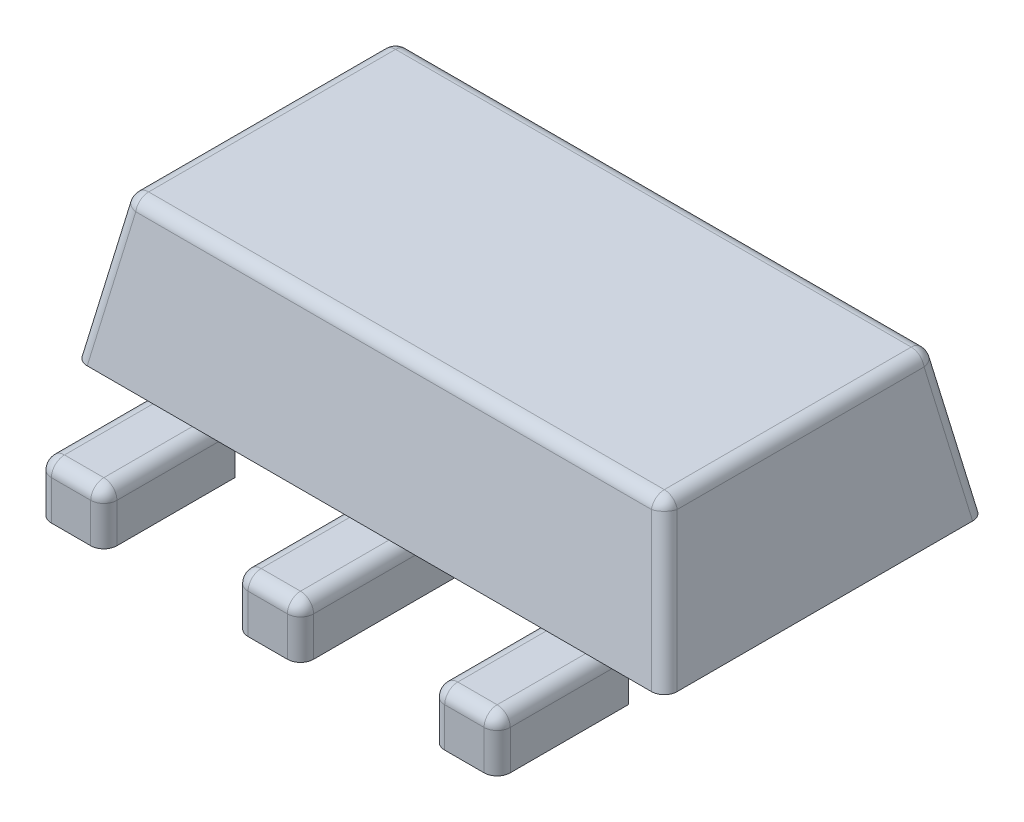
SolidWorks part; units mm, degrees
ref_plane "Спереди" through (0, 0, 0) normal (0, 0, 1) x (1, 0, 0)
ref_plane "Сверху" through (0, 0, 0) normal (0, 1, 0) x (1, 0, 0)
ref_plane "Справа" through (0, 0, 0) normal (1, 0, 0) x (0, 0, -1)
sketch "Эскиз1" plane through (0, 0, 0) normal (0, 1, 0) x (1, 0, 0)
  line L0 (-0.2499, -1) -> (-0.2499, -0.6205)
  line L1 (-1.75, -1) -> (-1.25, -1)
  line L2 (-1.75, -1) -> (-1.75, -2)
  line L3 (-1.75, -2) -> (-1.25, -2)
  line L4 (-1.25, -1) -> (-1.25, -2)
  line L5 (-1.75, -1) -> (-1.25, -2) construction
  line L6 (-1.75, -2) -> (-1.25, -1) construction
  line L7 (1.25, -1) -> (1.75, -1)
  line L8 (1.25, -1) -> (1.25, -2)
  line L9 (1.25, -2) -> (1.75, -2)
  line L10 (1.75, -1) -> (1.75, -2)
  line L11 (1.25, -1) -> (1.75, -2) construction
  line L12 (1.25, -2) -> (1.75, -1) construction
  line L13 (0.2499, -2) -> (-0.2499, -2)
  line L14 (0.2499, -2) -> (0.2499, -1)
  line L15 (-0.3378, -0.4084) -> (-0.7263, -0.02)
  line L16 (-0.2499, -2) -> (-0.2499, -1)
  line L17 (0.2499, -2) -> (-0.2499, -1) construction
  line L18 (0.2499, -1) -> (0.2499, -0.7278)
  line L19 (0.3179, -0.5376) -> (0.7462, -0.015)
  line L20 (0.2499, -1) -> (-0.2499, -2) construction
  line L21 (-0.5141, 2) -> (0.5141, 2)
  line L22 (-0.8141, 1.7) -> (-0.8141, 0.1922)
  line L25 (0.8141, 1.7) -> (0.8141, 0.1751)
  arc A0 (-0.2499, -0.6205) -> (-0.3378, -0.4084) centre (-0.5499, -0.6205) ccw
  arc A1 (0.2499, -0.7278) -> (0.3179, -0.5376) centre (0.5499, -0.7278) cw
  arc A2 (0.5141, 2) -> (0.8141, 1.7) centre (0.5141, 1.7) cw
  arc A3 (-0.8141, 1.7) -> (-0.5141, 2) centre (-0.5141, 1.7) cw
  arc A4 (0.7462, -0.015) -> (0.8141, 0.1751) centre (0.5141, 0.1751) ccw
  arc A5 (-0.7263, -0.02) -> (-0.8141, 0.1922) centre (-0.5141, 0.1922) cw
  point P0 (-1.5, -1.5)
  point P5 (1.5, -1.5)
  point P15 (0, 0.5)
  point P25 (0, 0)
  point P26 (0, -1.5)
  point P35 (0, 0)
  point P36 (0, 0)
  dimension "D1" = 0.3
  dimension "D2" = 0.3
  dimension "D3" = 0.3
  dimension "D4" = 0.3
extrude "Бобышка-Вытянуть1" add sketch "Эскиз1" along normal blind 0.4
fillet "Скругление1" radius 0.1 16 edges at (-0.532, 0.4, 0.2142) (-0.7913, 0.4, -0.0774) (-0.8141, 0.4, -0.9461) (-0.7263, 0.4, -1.9121) (0, 0.4, -2) (0.7263, 0.4, -1.9121) (0.8141, 0.4, -0.9376) (0.7966, 0.4, -0.0742) (0.532, 0.4, 0.2763) (0.2674, 0.4, 0.6268) (0.2499, 0.4, 1.3639) (0, 0.4, 2) (-0.2499, 0.4, 1.3103) (-0.2728, 0.4, 0.5057) (0.2499, 0.2, 2) (-0.2499, 0.2, 2)
fillet "Скругление2" radius 0.1 6 edges at (-1.5, 0.4, 2) (-1.75, 0.4, 1.5) (-1.5, 0.4, 1) (-1.25, 0.4, 1.5) (-1.25, 0.2, 2) (-1.75, 0.2, 2)
fillet "Скругление3" radius 0.1 6 edges at (1.5, 0.4, 2) (1.25, 0.4, 1.5) (1.5, 0.4, 1) (1.75, 0.4, 1.5) (1.75, 0.2, 2) (1.25, 0.2, 2)
sketch "Эскиз2" plane through (0, 0.4, 0) normal (0, 1, 0) x (1, 0, 0)
  line L1 (-2.25, 1.225) -> (2.25, 1.225)
  line L2 (-2.25, 1.225) -> (-2.25, -1.225)
  line L3 (-2.25, -1.225) -> (2.25, -1.225)
  line L4 (2.25, 1.225) -> (2.25, -1.225)
  line L5 (-2.25, 1.225) -> (2.25, -1.225) construction
  line L6 (-2.25, -1.225) -> (2.25, 1.225) construction
  point P0 (0, 0)
extrude "Бобышка-Вытянуть2" add sketch "Эскиз2" along normal blind 1.1 separate body
chamfer "Фаска1" distance 1.1 distance2 0.2 4 edges at (0, 1.5, 1.225) (-2.25, 1.5, 0) (0, 1.5, -1.225) (2.25, 1.5, 0) first distance on face at (0, 0.95, 1.225) first distance on face at (-2.25, 0.95, 0) first distance on face at (0, 0.95, -1.225) first distance on face at (2.25, 0.95, 0)
fillet "Скругление4" radius 0.1 8 edges at (0, 1.5, -1.025) (2.05, 1.5, 0) (0, 1.5, 1.025) (-2.05, 1.5, 0) (-2.15, 0.95, -1.125) (-2.15, 0.95, 1.125) (2.15, 0.95, -1.125) (2.15, 0.95, 1.125)
